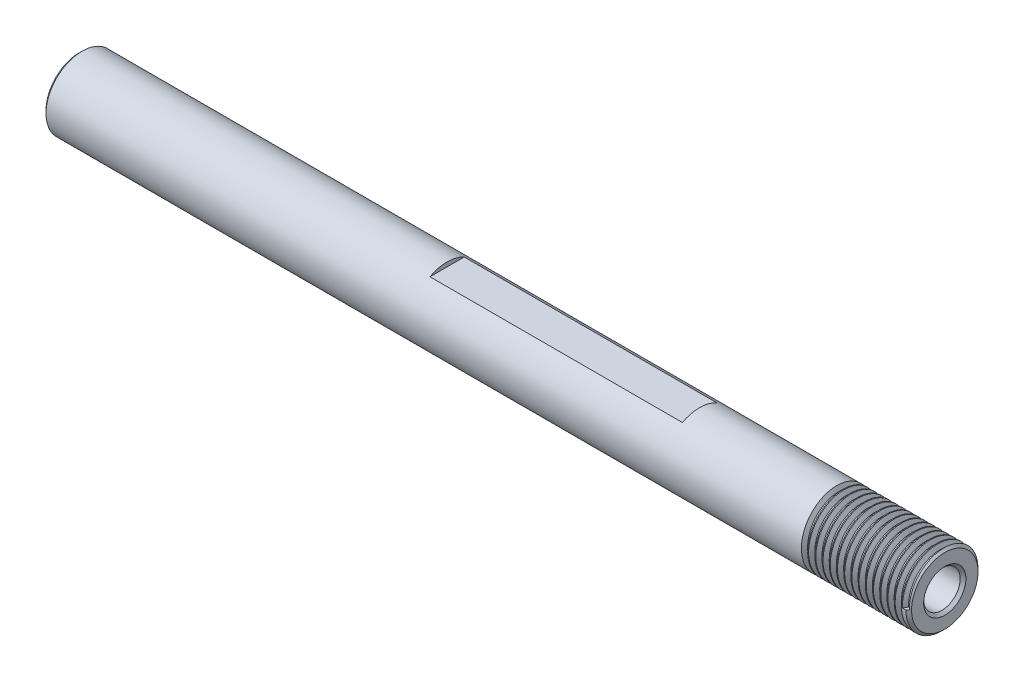
SolidWorks part; units mm, degrees
material "Copper"
ref_plane "Front Plane" through (0, 0, 0) normal (0, 0, 1) x (1, 0, 0)
ref_plane "Top Plane" through (0, 0, 0) normal (0, 1, 0) x (1, 0, 0)
ref_plane "Right Plane" through (0, 0, 0) normal (1, 0, 0) x (0, 0, -1)
sketch "Sketch2" plane through (0, 0, 0) normal (1, 0, 0) x (0, 0, -1)
  circle A0 centre (0, 0) radius 6.35
  circle A1 centre (0, 0) radius 3.2195
extrude "Boss-Extrude1" add sketch "Sketch2" along normal blind 152.4
thread "Thread2" pitch 1.27 method cut profile "Thread Profile2" start angle 0, offset 0, length 18.2563, pitch 1.27, diameter 12.7
ref_plane "Plane2" through (152.4, 0, 6.35) normal (0, -1, 0) x (0, 0, 1)
sketch "Thread Profile2" plane through (152.4, 0, 6.35) normal (0, -1, 0) x (0, 0, 1)
  line L0 (0, 0) -> (0, 1.27) construction
  line L11 (0, 0) -> (0, 1.1112)
  line L12 (0, 1.1112) -> (-0.6874, 0.7144)
  line L13 (-0.6874, 0.7144) -> (-0.6874, 0.3969)
  line L15 (-0.6874, 0.3969) -> (0, 0)
  line L17 (-0.6874, 0.5556) -> (0, 0.5556) construction
  point P2 (0, 0)
  dimension "Pitch" = 1.27
  dimension "Profile_Angle" = 60
  dimension "Profile_Land" = 0.3175
  dimension "Profile_Height" = 0.6874
chamfer "Chamfer3" distance 0.5 angle 45 4 edges at (0, 0, -6.35) (0, 0, -3.2195) (152.4, 0, 6.35) (152.4, 0, -3.2195)
sketch "Sketch5" plane through (0, 0, 0) normal (0, 0, 1) x (1, 0, 0)
  line L1 (109.22, 5.588) -> (64.77, 5.588)
  line L2 (109.22, 5.588) -> (109.22, 6.35)
  line L3 (109.22, 6.35) -> (64.77, 6.35)
  line L4 (64.77, 5.588) -> (64.77, 6.35)
  line L6 (152.4, -5.85) -> (152.4, 5.85) construction
  line L7 (133.1913, 6.35) -> (0.5, 6.35) construction
  line L8 (0.5, -6.35) -> (133.8262, -6.35) construction
  line L9 (109.22, -5.588) -> (64.77, -5.588)
  line L10 (109.22, -5.588) -> (109.22, -6.35)
  line L11 (109.22, -6.35) -> (64.77, -6.35)
  line L12 (64.77, -5.588) -> (64.77, -6.35)
  dimension "D1" = 11.176
  dimension "D2" = 43.18
  dimension "D3" = 44.45
extrude "Cut-Extrude1" cut sketch "Sketch5" against normal through all both and the other way through all
